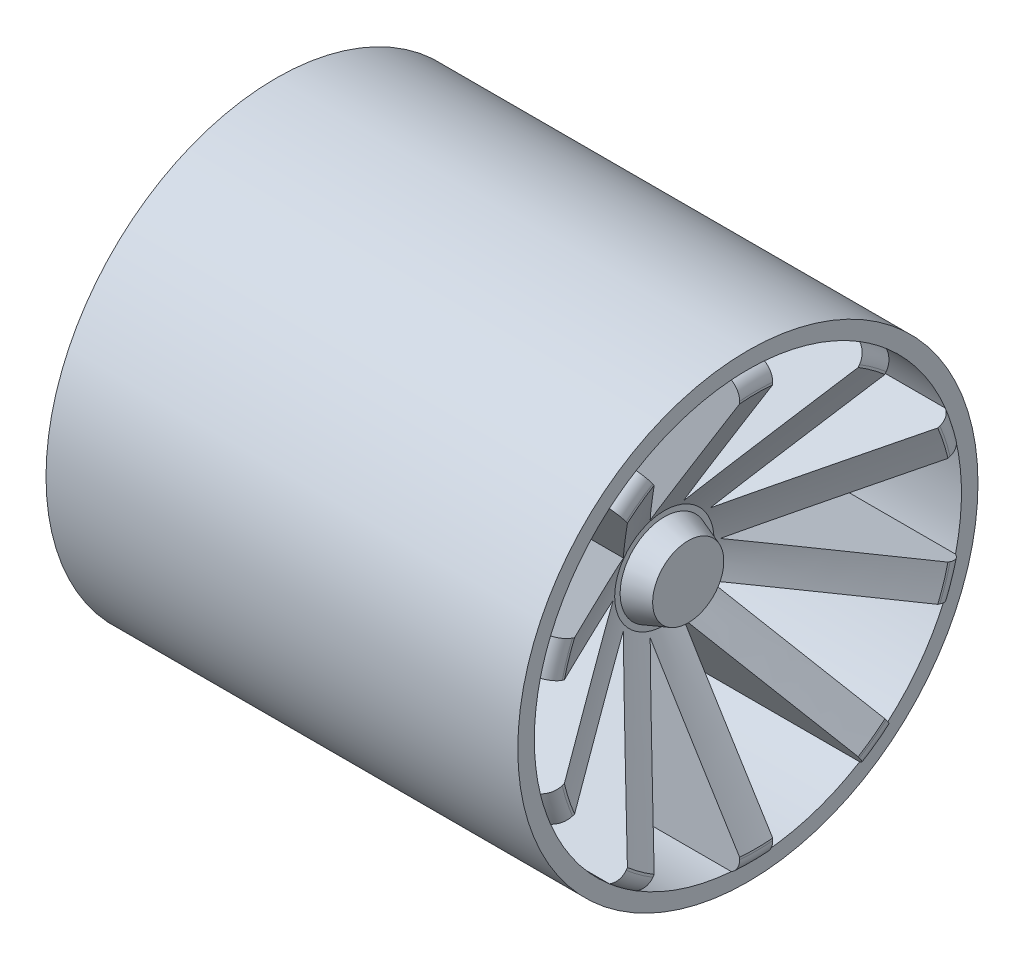
SolidWorks part; units mm, degrees
ref_plane "Front Plane" through (0, 0, 0) normal (0, 0, 1) x (1, 0, 0)
ref_plane "Top Plane" through (0, 0, 0) normal (0, 1, 0) x (1, 0, 0)
ref_plane "Right Plane" through (0, 0, 0) normal (1, 0, 0) x (0, 0, -1)
sketch "Sketch1" plane through (0, 0, 0) normal (0, 1, 0) x (1, 0, 0)
  line L0 (-25, 0) -> (25, 0) construction
  line L1 (0, 28.4532) -> (0, -32.9737) construction
  line L2 (-14.5, 13.9) -> (14, 13.9)
  line L3 (-14.5, 13.9) -> (-14.5, 12.9)
  line L4 (-14.5, 12.9) -> (-6.2391, 12.9)
  line L5 (-6.2391, 12.9) -> (-6.2391, 3.6)
  line L6 (-6.2391, 3.6) -> (-11.8743, 3.6)
  line L7 (-11.8743, 3.6) -> (-11.8743, 1.6)
  line L8 (-11.8743, 1.6) -> (-6.573, 1.6)
  line L9 (-6.573, 1.6) -> (-6.573, 0)
  line L10 (-6.573, 0) -> (1.974, 0)
  line L11 (1.974, 0) -> (8.9523, 0)
  line L12 (8.9523, 2.6716) -> (8.9523, 3)
  line L13 (8.9523, 3) -> (14.5, 11.9)
  line L14 (14.5, 12.9) -> (14.5, 11.9)
  line L15 (8.9523, 2.6716) -> (10.3949, 2.1495)
  line L17 (10.3949, 0) -> (8.9523, 0)
  line L18 (10.3949, 2.1495) -> (10.3949, 0)
  line L19 (14.5, 12.9) -> (14, 12.9)
  line L20 (14, 12.9) -> (14, 13.9)
  dimension "D1" = 50
  dimension "D2" = 25
  dimension "D3" = 27.8
  dimension "D6" = 3
  dimension "D8" = 3.2
  dimension "D9" = 2
  dimension "D10" = 1
  dimension "D11" = 0.5
revolve "Revolve1" add sketch "Sketch1" angle 360 about L0
sketch "Sketch2" plane through (14.5, 0, 0) normal (1, 0, 0) x (0, 0, -1)
  line L0 (0, 11.9) -> (0, -11.9) construction
  line L1 (-11.9, 0) -> (11.9, 0) construction
  line L36 (-1, 12.8612) -> (-1, 3.0777)
  line L37 (1, 3.0777) -> (1, 12.8612)
  line L38 (2.618, 1.9021) -> (8.3686, 9.8171)
  line L39 (6.7506, 10.9927) -> (1, 3.0777)
  line L40 (3.2361, 0) -> (12.5407, 3.0233)
  line L41 (11.9227, 4.9254) -> (2.618, 1.9021)
  line L42 (2.618, -1.9021) -> (11.9227, -4.9254)
  line L43 (12.5407, -3.0233) -> (3.2361, 0)
  line L44 (1, -3.0777) -> (6.7506, -10.9927)
  line L45 (8.3686, -9.8171) -> (2.618, -1.9021)
  line L46 (-1, -3.0777) -> (-1, -12.8612)
  line L47 (1, -12.8612) -> (1, -3.0777)
  line L48 (-2.618, -1.9021) -> (-8.3686, -9.8171)
  line L49 (-6.7506, -10.9927) -> (-1, -3.0777)
  line L50 (-3.2361, 0) -> (-12.5407, -3.0233)
  line L51 (-11.9227, -4.9254) -> (-2.618, -1.9021)
  line L52 (-2.618, 1.9021) -> (-11.9227, 4.9254)
  line L53 (-12.5407, 3.0233) -> (-3.2361, 0)
  line L54 (-1, 3.0777) -> (-6.7506, 10.9927)
  line L55 (-8.3686, 9.8171) -> (-2.618, 1.9021)
  circle A2 centre (0, 0) radius 11.9 construction
  circle A4 centre (0, 0) radius 12.9 construction
  arc A61 (-8.3686, 9.8171) -> (-11.9227, 4.9254) centre (0, 0) ccw
  arc A63 (-1, 12.8612) -> (-6.7506, 10.9927) centre (0, 0) ccw
  arc A64 (6.7506, 10.9927) -> (1, 12.8612) centre (0, 0) ccw
  arc A65 (8.3686, -9.8171) -> (11.9227, -4.9254) centre (0, 0) ccw
  arc A66 (1, -12.8612) -> (6.7506, -10.9927) centre (0, 0) ccw
  arc A67 (-6.7506, -10.9927) -> (-1, -12.8612) centre (0, 0) ccw
  arc A68 (-11.9227, -4.9254) -> (-8.3686, -9.8171) centre (0, 0) ccw
  arc A69 (-12.5407, 3.0233) -> (-12.5407, -3.0233) centre (0, 0) ccw
  arc A72 (12.5407, -3.0233) -> (12.5407, 3.0233) centre (0, 0) ccw
  arc A73 (11.9227, 4.9254) -> (8.3686, 9.8171) centre (0, 0) ccw
  point P54 (0, 0)
  point P80 (0, 0)
  circle M4 centre (0, 0) radius 11.9
  circle M77 centre (0, 0) radius 12.9
  dimension "D2" = 1
  dimension "D1" = 2
  dimension "D3" = 10
extrude "Cut-Extrude1" cut sketch "Sketch2" against normal through all both and the other way through all contours L39 L37 M77 M4 | L39 L37 M4 | L54 L36 M4 | L54 L36 M4 M77 | L55 L52 M4 | L53 L50 M77 M4 | L53 L50 M4 | L51 L48 M77 M4 | L51 L48 M4 | L49 L46 M77 M4 | L49 L46 M4 | L47 L44 M77 M4 | L47 L44 M4 | L45 L42 M4 | L45 L42 M77 M4 | L43 L40 M4 | L43 L40 M77 M4 | L41 L38 M4 | L41 L38 M77 M4 | A61 L52 L55 region at (14.5, 11.6948, 3.7999) region at (14.5, 8.5044, 2.7632) region at (14.5, 11.6948, -3.7999) region at (14.5, 8.5044, -2.7632) region at (14.5, 5.256, 7.2343) region at (14.5, 7.2278, -9.9482) region at (14.5, 5.256, -7.2343) region at (14.5, 0, 12.2966) region at (14.5, 0, 8.9421) region at (14.5, 0, -12.2966) region at (14.5, 0, -8.9421) region at (14.5, -7.2278, 9.9482) region at (14.5, -5.256, 7.2343) region at (14.5, -11.6948, 3.7999) region at (14.5, -7.2278, -9.9482) region at (14.5, -5.256, -7.2343) region at (14.5, -8.5044, 2.7632) region at (14.5, -11.6948, -3.7999) region at (14.5, -8.5044, -2.7632)
fillet "Fillet2" radius 1 10 edges at (14.5, 10.4363, 7.5824) (14.5, 3.9863, 12.2686) (14.5, -3.9863, 12.2686) (14.5, -10.4363, 7.5824) (14.5, -12.9, 0) (14.5, -10.4363, -7.5824) (14.5, -3.9863, -12.2686) (14.5, 3.9863, -12.2686) (14.5, 10.4363, -7.5824) (14.5, 12.9, 0)
